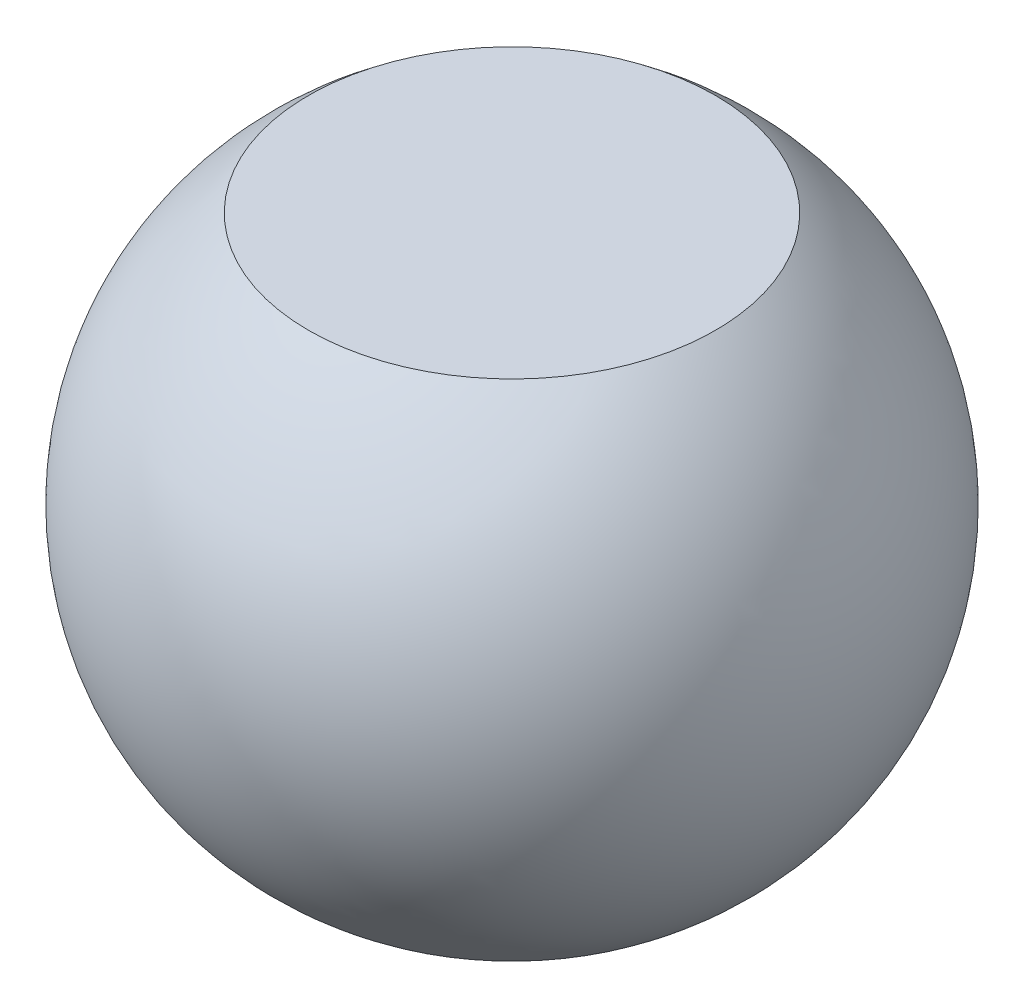
SolidWorks part; units mm, degrees
ref_plane "Front Plane" through (0, 0, 0) normal (0, 0, 1) x (1, 0, 0)
ref_plane "Top Plane" through (0, 0, 0) normal (0, 1, 0) x (1, 0, 0)
ref_plane "Right Plane" through (0, 0, 0) normal (1, 0, 0) x (0, 0, -1)
sketch "Sketch2" plane through (0, 0, 0) normal (1, 0, 0) x (0, 0, -1)
  line L0 (0, 0) -> (0, 805) construction
  line L1 (0, 0) -> (323, 0) construction
  line L2 (323, 0) -> (0, 0)
  line L3 (0, 805) -> (324.4168, 805)
  line L4 (0, 0) -> (0, 805)
  arc A0 (323, 0) -> (324.4168, 805) centre (23.7135, 403.028) ccw
  dimension "D3" = 502
  dimension "D1" = 323
  dimension "D2" = 805
revolve "Revolve1" add sketch "Sketch2" angle 360 about L4
sketch "Sketch3" plane through (0, 0, 0) normal (0, 0, 1) x (1, 0, 0)
  line L0 (-972.6037, 707.501) -> (-899.8067, 780.298)
  arc A0 (-433, 112.3589) -> (-460.307, 650.7983) centre (-23.7135, 403.028) cw
  arc A1 (-324.4168, 805) -> (-323, 0) centre (-23.7135, 403.028) ccw construction
  arc A2 (-972.6037, 707.501) -> (-494.8637, 229.7609) centre (-972.6037, 229.7609) cw
  arc A3 (-899.8067, 780.298) -> (-460.307, 650.7983) centre (-842.4446, 164.432) cw
  dimension "D1" = 433
